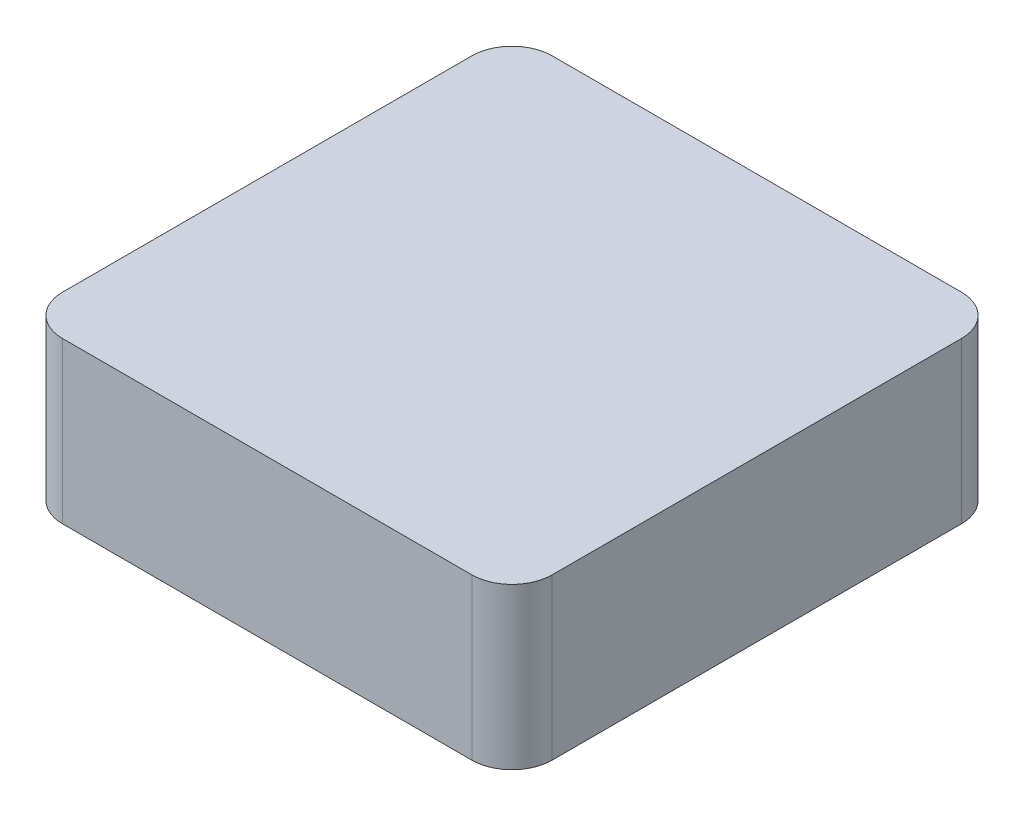
SolidWorks part; units mm, degrees
ref_plane "Alzado" through (0, 0, 0) normal (0, 0, 1) x (1, 0, 0)
ref_plane "Planta" through (0, 0, 0) normal (0, 1, 0) x (1, 0, 0)
ref_plane "Vista lateral" through (0, 0, 0) normal (1, 0, 0) x (0, 0, -1)
sketch "Croquis1" plane through (0, 0, 0) normal (0, 1, 0) x (1, 0, 0)
  line L1 (30.5, -30.5) -> (-30.5, -30.5)
  line L2 (30.5, -30.5) -> (30.5, 30.5)
  line L3 (30.5, 30.5) -> (-30.5, 30.5)
  line L4 (-30.5, -30.5) -> (-30.5, 30.5)
  line L5 (30.5, -30.5) -> (-30.5, 30.5) construction
  line L6 (30.5, 30.5) -> (-30.5, -30.5) construction
  point P0 (0, 0)
  dimension "D1" = 61
  dimension "D2" = 61
extrude "Saliente-Extruir1" add sketch "Croquis1" along normal blind 20
fillet "Redondeo1" radius 5 4 edges at (-30.5, 10, -30.5) (30.5, 10, -30.5) (-30.5, 10, 30.5) (30.5, 10, 30.5)
